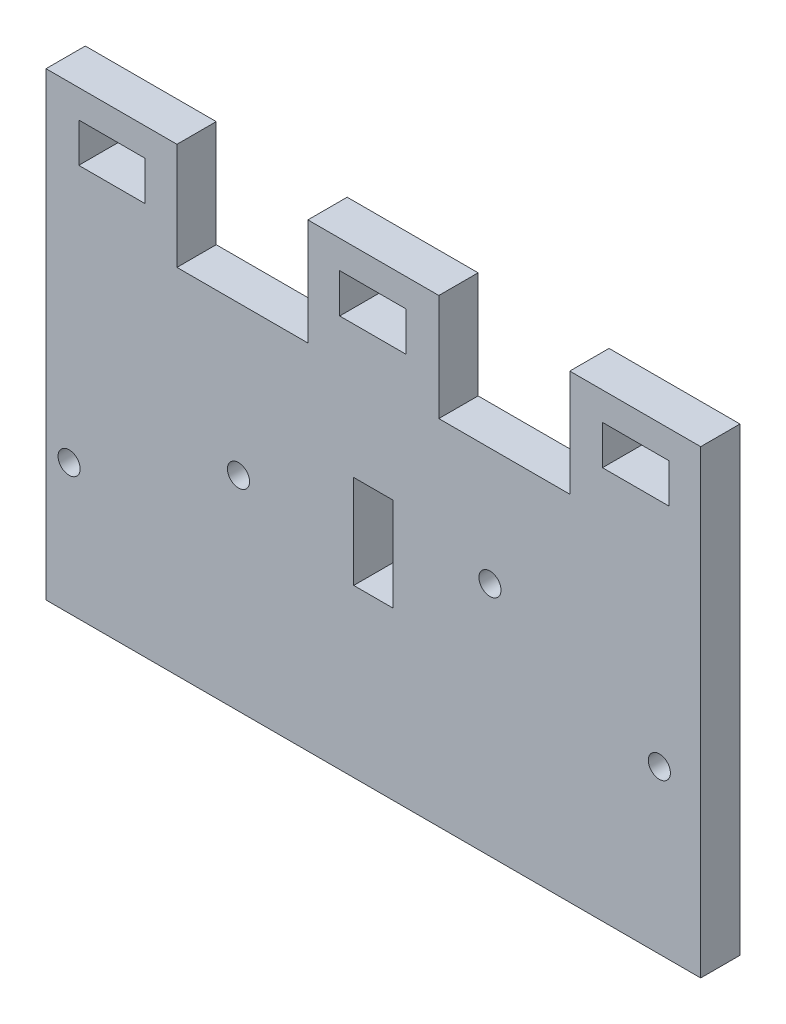
SolidWorks part; units mm, degrees
ref_plane "Front Plane" through (0, 0, 0) normal (0, 0, 1) x (1, 0, 0)
ref_plane "Top Plane" through (0, 0, 0) normal (0, 1, 0) x (1, 0, 0)
ref_plane "Right Plane" through (0, 0, 0) normal (1, 0, 0) x (0, 0, -1)
sketch "Sketch1" plane through (0, 0, 0) normal (0, 0, 1) x (1, 0, 0)
  line L1 (-39.3603, 14.4208) -> (49.5397, 14.4208)
  line L2 (-39.3603, 14.4208) -> (-39.3603, -48.0632)
  line L3 (-39.3603, -48.0632) -> (49.5397, -48.0632)
  line L4 (49.5397, 14.4208) -> (49.5397, -48.0632)
  dimension "D1" = 88.9
  dimension "D2" = 62.484
extrude "Boss-Extrude1" add sketch "Sketch1" along normal blind 5.334
sketch "Sketch2" plane through (0, 0, 5.334) normal (0, 0, 1) x (1, 0, 0)
  line L0 (49.5397, 14.4208) -> (-39.3603, 14.4208) construction
  line L1 (-21.5803, 14.4208) -> (-3.8003, 14.4208)
  line L2 (-21.5803, 14.4208) -> (-21.5803, -0.0572)
  line L3 (-21.5803, -0.0572) -> (-3.8003, -0.0572)
  line L4 (-3.8003, 14.4208) -> (-3.8003, -0.0572)
  line L5 (-21.5803, -0.0572) -> (-39.3603, -0.0572) construction
  line L6 (13.9797, 14.4208) -> (31.7597, 14.4208)
  line L7 (13.9797, 14.4208) -> (13.9797, -0.0572)
  line L8 (13.9797, -0.0572) -> (31.7597, -0.0572)
  line L9 (31.7597, 14.4208) -> (31.7597, -0.0572)
  line L10 (-39.3603, 14.4208) -> (-39.3603, -48.0632) construction
  line L11 (-3.8003, -0.0572) -> (13.9797, -0.0572) construction
  line L12 (31.7597, -0.0572) -> (49.5397, -0.0572) construction
  line L13 (49.5397, -48.0632) -> (49.5397, 14.4208) construction
  dimension "D1" = 14.478
extrude "Cut-Extrude1" cut sketch "Sketch2" against normal through all
sketch "Sketch3" plane through (0, 0, 5.334) normal (0, 0, 1) x (1, 0, 0)
  line L0 (-21.5803, 14.4208) -> (-39.3603, 14.4208) construction
  line L1 (-34.9153, 10.6108) -> (-25.8983, 10.6108)
  line L2 (-34.9153, 10.6108) -> (-34.9153, 5.2768)
  line L3 (-34.9153, 5.2768) -> (-25.8983, 5.2768)
  line L4 (-25.8983, 10.6108) -> (-25.8983, 5.2768)
  line L6 (-39.3603, 14.4208) -> (-39.3603, -48.0632) construction
  line L7 (-21.5803, 14.4208) -> (-21.5803, -0.0572) construction
  line L8 (-12.6903, -0.0572) -> (-12.6903, 17.5431) construction
  line L9 (-21.5803, -0.0572) -> (-3.8003, -0.0572) construction
  line L10 (22.8697, -0.0572) -> (22.8697, 18.5459) construction
  line L11 (13.9797, -0.0572) -> (31.7597, -0.0572) construction
  line L12 (0.5177, 10.6108) -> (0.5177, 5.2768)
  line L13 (9.5347, 5.2768) -> (0.5177, 5.2768)
  line L14 (9.5347, 10.6108) -> (9.5347, 5.2768)
  line L15 (9.5347, 10.6108) -> (0.5177, 10.6108)
  line L16 (36.2047, 10.6108) -> (45.2217, 10.6108)
  line L17 (36.2047, 10.6108) -> (36.2047, 5.2768)
  line L18 (36.2047, 5.2768) -> (45.2217, 5.2768)
  line L19 (45.2217, 10.6108) -> (45.2217, 5.2768)
  dimension "D1" = 3.81
  dimension "D2" = 5.334
  dimension "D3" = 4.445
  dimension "D4" = 4.318
extrude "Cut-Extrude2" cut sketch "Sketch3" against normal through all
sketch "Sketch5" plane through (0, 0, 5.334) normal (0, 0, 1) x (1, 0, 0)
  line L0 (5.0897, 14.4208) -> (5.0897, -48.0632) construction
  line L1 (2.4227, -12.7572) -> (7.7567, -12.7572)
  line L2 (2.4227, -12.7572) -> (2.4227, -25.4572)
  line L3 (2.4227, -25.4572) -> (7.7567, -25.4572)
  line L4 (7.7567, -12.7572) -> (7.7567, -25.4572)
  line L5 (13.9797, 14.4208) -> (-3.8003, 14.4208) construction
  line L6 (-39.3603, -48.0632) -> (49.5397, -48.0632) construction
  line L7 (13.9797, -0.0572) -> (31.7597, -0.0572) construction
  dimension "D1" = 5.334
  dimension "D2" = 12.7
  dimension "D3" = 12.7
  dimension "D4" = 2.667
extrude "Cut-Extrude3" cut sketch "Sketch5" against normal through all
sketch "Sketch6" plane through (0, 0, 5.334) normal (0, 0, 1) x (1, 0, 0)
  line L12 (13.9797, -0.0572) -> (13.9797, 14.4208)
  line L13 (13.9797, 14.4208) -> (-3.8003, 14.4208)
  line L14 (-3.8003, 14.4208) -> (-3.8003, -0.0572)
  line L15 (-3.8003, -0.0572) -> (-21.5803, -0.0572)
  line L16 (-21.5803, -0.0572) -> (-21.5803, 14.4208)
  line L17 (-21.5803, 14.4208) -> (-39.3603, 14.4208)
  line L18 (-39.3603, 14.4208) -> (-39.3603, -48.0632)
  line L19 (-39.3603, -48.0632) -> (49.5397, -48.0632)
  line L20 (49.5397, -48.0632) -> (49.5397, 14.4208)
  line L21 (49.5397, 14.4208) -> (31.7597, 14.4208)
  line L22 (31.7597, 14.4208) -> (31.7597, -0.0572)
  line L23 (31.7597, -0.0572) -> (13.9797, -0.0572)
  line L24 (13.9797, -0.0572) -> (13.9797, 14.4208)
  line L25 (13.9797, 14.4208) -> (-3.8003, 14.4208)
  line L26 (-3.8003, 14.4208) -> (-3.8003, -0.0572)
  line L27 (-3.8003, -0.0572) -> (-21.5803, -0.0572)
  line L28 (-21.5803, -0.0572) -> (-21.5803, 14.4208)
  line L29 (-21.5803, 14.4208) -> (-39.3603, 14.4208)
  line L30 (-39.3603, 14.4208) -> (-39.3603, -48.0632)
  line L31 (-39.3603, -48.0632) -> (49.5397, -48.0632)
  line L32 (49.5397, -48.0632) -> (49.5397, 14.4208)
  line L33 (49.5397, 14.4208) -> (31.7597, 14.4208)
  line L34 (31.7597, 14.4208) -> (31.7597, -0.0572)
  line L35 (31.7597, -0.0572) -> (13.9797, -0.0572)
  dimension "D1" = 0
sketch "Sketch7" plane through (0, 0, 5.334) normal (0, 0, 1) x (1, 0, 0)
  line L12 (13.9797, -0.0572) -> (13.9797, 14.4208)
  line L13 (13.9797, 14.4208) -> (-3.8003, 14.4208)
  line L14 (-3.8003, 14.4208) -> (-3.8003, -0.0572)
  line L15 (-3.8003, -0.0572) -> (-21.5803, -0.0572)
  line L16 (-21.5803, -0.0572) -> (-21.5803, 14.4208)
  line L17 (-21.5803, 14.4208) -> (-39.3603, 14.4208)
  line L18 (-39.3603, 14.4208) -> (-39.3603, -48.0632)
  line L19 (-39.3603, -48.0632) -> (49.5397, -48.0632)
  line L20 (49.5397, -48.0632) -> (49.5397, 14.4208)
  line L21 (49.5397, 14.4208) -> (31.7597, 14.4208)
  line L22 (31.7597, 14.4208) -> (31.7597, -0.0572)
  line L23 (31.7597, -0.0572) -> (13.9797, -0.0572)
  line L24 (13.9797, -0.0572) -> (13.9797, 14.4208)
  line L25 (13.9797, 14.4208) -> (-3.8003, 14.4208)
  line L26 (-3.8003, 14.4208) -> (-3.8003, -0.0572)
  line L27 (-3.8003, -0.0572) -> (-21.5803, -0.0572)
  line L28 (-21.5803, -0.0572) -> (-21.5803, 14.4208)
  line L29 (-21.5803, 14.4208) -> (-39.3603, 14.4208)
  line L30 (-39.3603, 14.4208) -> (-39.3603, -48.0632)
  line L31 (-39.3603, -48.0632) -> (49.5397, -48.0632)
  line L32 (49.5397, -48.0632) -> (49.5397, 14.4208)
  line L33 (49.5397, 14.4208) -> (31.7597, 14.4208)
  line L34 (31.7597, 14.4208) -> (31.7597, -0.0572)
  line L35 (31.7597, -0.0572) -> (13.9797, -0.0572)
  circle A0 centre (-36.2253, -30.3292) radius 1.5 construction
  circle A1 centre (-13.2253, -20.3292) radius 1.5 construction
  circle A2 centre (20.9247, -16.0112) radius 1.5 construction
  circle A3 centre (43.9247, -26.0112) radius 1.5 construction
  circle A4 centre (-36.2253, -30.3292) radius 1.5
  circle A5 centre (-13.2253, -20.3292) radius 1.5
  circle A6 centre (20.9247, -16.0112) radius 1.5
  circle A7 centre (43.9247, -26.0112) radius 1.5
  dimension "D1" = 0
extrude "Cut-Extrude4" cut sketch "Sketch7" against normal through all contours A4 | A6 | A7 | A5 region at (-36.2253, -30.3292, 5.334) region at (20.9247, -16.0112, 5.334) region at (43.9247, -26.0112, 5.334)
equation "\"MDF\"= .21in"
equation "\"Foamcore\"= .13in"
equation "\"Gmaterial\"= \"MDF\""
equation "\"D1@Boss-Extrude1\"=\"MDF\""
equation "\"D1@Sketch2\"=2*\"MDF\"+.15"
equation "\"D2@Sketch3\"=\"MDF\""
equation "\"D1@Sketch5\"=\"MDF\""
equation "\"D4@Sketch5\"=\"MDF\"/2"
